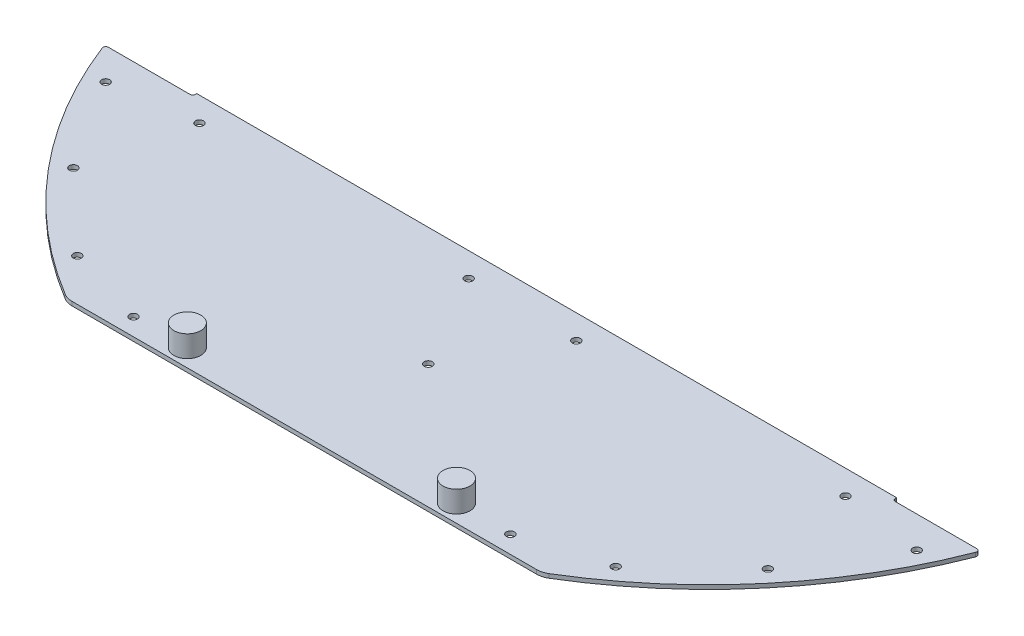
SolidWorks part; units mm, degrees
material "3.3535 (EN-AW 5754)"
ref_plane "Plan de face" through (0, 0, 0) normal (0, 0, 1) x (1, 0, 0)
ref_plane "Plan de dessus" through (0, 0, 0) normal (0, 1, 0) x (1, 0, 0)
ref_plane "Plan de droite" through (0, 0, 0) normal (1, 0, 0) x (0, 0, -1)
sketch "Esquisse1" plane through (0, 0, 0) normal (0, 1, 0) x (1, 0, 0)
  line L0 (0, 0) -> (0, -150) construction
  line L1 (-130, -60) -> (130, -60)
  line L2 (130, -60) -> (130, -61.5)
  line L3 (-88.1816, -150) -> (88.1816, -150)
  line L6 (162.769, -61.5) -> (130, -61.5)
  line L8 (-162.769, -61.5) -> (-130, -61.5)
  line L9 (-130, -60) -> (-130, -61.5)
  circle A0 centre (-120, -69) radius 1.5
  circle A1 centre (-20, -69) radius 1.5
  circle A2 centre (20, -69) radius 1.5
  circle A3 centre (120, -69) radius 1.5
  circle A4 centre (0, -104) radius 1.5
  arc A10 (-162.769, -61.5) -> (-88.1816, -150) centre (0, 0) ccw
  arc A11 (88.1816, -150) -> (162.769, -61.5) centre (0, 0) ccw
  dimension "D2" = 60
  dimension "D3" = 9
  dimension "D4" = 3
  dimension "D5" = 240
  dimension "D7" = 40
  dimension "D8" = 44
  dimension "D10" = 260
  dimension "D12" = 1.5
  dimension "D13" = 348
  dimension "D6" = 150
extrude "Boss.-Extru.1" add sketch "Esquisse1" along normal blind 1.5
fillet "Congé1" radius 7 2 edges at (88.1816, 0.75, 150) (-88.1816, 0.75, 150)
fillet "Congé2" radius 1 4 edges at (-130, 0.75, 61.5) (130, 0.75, 61.5) (162.769, 0.75, 61.5) (-162.769, 0.75, 61.5)
sketch "Esquisse2" plane through (0, 1.5, 0) normal (0, 1, 0) x (1, 0, 0)
  line L0 (-150.6593, -73.1985) -> (-129.0082, -106.8322) construction
  line L1 (-129.0082, -106.8322) -> (-100, -134.3735) construction
  line L2 (0, 0) -> (0, -150) construction
  line L3 (-86.2554, -150) -> (86.2554, -150) construction
  circle A0 centre (-150.6593, -73.1985) radius 1.5
  circle A1 centre (-129.0082, -106.8322) radius 1.5
  circle A2 centre (-100, -134.3735) radius 1.5
  circle A3 centre (-70, -143.5) radius 1.5
  circle A4 centre (-50, -143.5) radius 1.5
  circle A5 centre (0, 0) radius 167.5 construction
  circle A6 centre (150.6593, -73.1985) radius 1.5
  circle A7 centre (129.0082, -106.8322) radius 1.5
  circle A8 centre (100, -134.3735) radius 1.5
  circle A9 centre (70, -143.5) radius 1.5
  circle A10 centre (50, -143.5) radius 1.5
  arc A11 (-162.2481, -62.8613) -> (-89.8709, -148.994) centre (0, 0) ccw construction
  dimension "D1" = 40
  dimension "D2" = 3
  dimension "D4" = 6.5
  dimension "D5" = 140
  dimension "D6" = 100
  dimension "D7" = 6.5
  dimension "D3" = 100
extrude "Enlèv. mat.-Extru.1" cut sketch "Esquisse2" against normal through all
sketch "Esquisse3" plane through (0, 1.5, 0) normal (0, 1, 0) x (1, 0, 0)
  circle A0 centre (-50, -143.5) radius 5
  circle A1 centre (50, -143.5) radius 5
  circle A2 centre (-50, -143.5) radius 1.5 construction
  circle A3 centre (50, -143.5) radius 1.5 construction
  point P4 (0, 0)
  point P7 (0, 0)
  dimension "D1" = 10
extrude "Boss.-Extru.2" add sketch "Esquisse3" along normal blind 8 separate body
